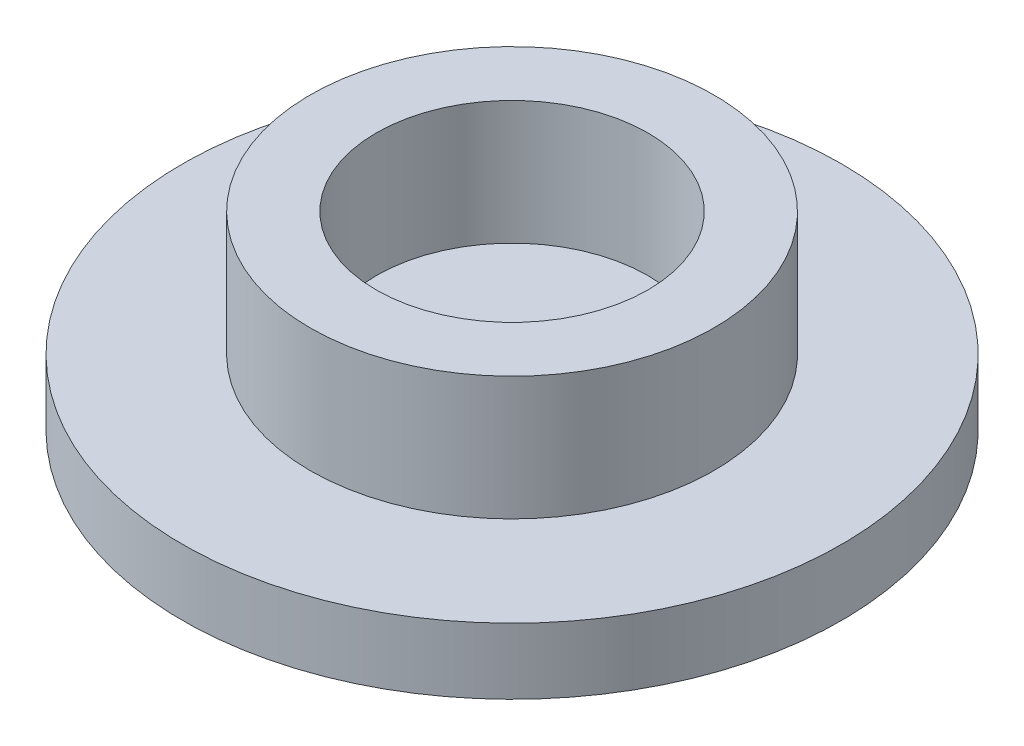
SolidWorks part; units mm, degrees
ref_plane "Front Plane" through (0, 0, 0) normal (0, 0, 1) x (1, 0, 0)
ref_plane "Top Plane" through (0, 0, 0) normal (0, 1, 0) x (1, 0, 0)
ref_plane "Right Plane" through (0, 0, 0) normal (1, 0, 0) x (0, 0, -1)
sketch "Sketch1" plane through (0, 0, 0) normal (0, 1, 0) x (1, 0, 0)
  circle A0 centre (0, 0) radius 1.65
  circle A1 centre (0, 0) radius 2.45
  dimension "D1" = 3.3
  dimension "D2" = 4.9
extrude "Boss-Extrude1" add sketch "Sketch1" along normal blind 1.5
sketch "Sketch2" plane through (0, 0, 0) normal (0, -1, 0) x (1, 0, 0)
  circle A0 centre (0, 0) radius 4
  dimension "D1" = 8
extrude "Boss-Extrude2" add sketch "Sketch2" along normal blind 0.8
